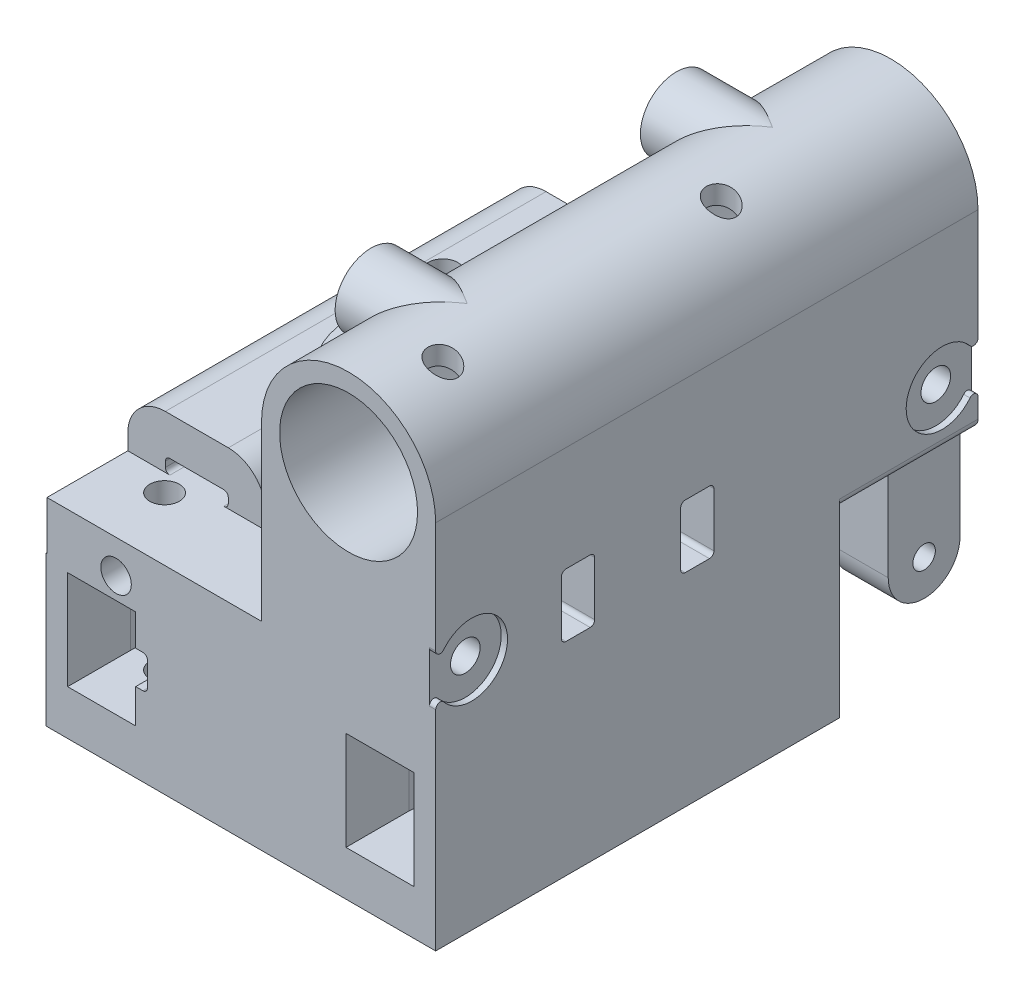
SolidWorks part; units mm, degrees
ref_plane "Front Plane" through (0, 0, 0) normal (0, 0, 1) x (1, 0, 0)
ref_plane "Top Plane" through (0, 0, 0) normal (0, 1, 0) x (1, 0, 0)
ref_plane "Right Plane" through (0, 0, 0) normal (1, 0, 0) x (0, 0, -1)
sketch "Sketch1" plane through (0, 0, 0) normal (0, 0, 1) x (1, 0, 0)
  line L57 (9.7, 0) -> (9.7, -41.3)
  line L61 (-29.4, -32) -> (-29.4, -29.3)
  line L62 (-29.4, -18.1) -> (-29.4, -18.7)
  line L63 (-28.9, -19.2) -> (-22.9, -19.2)
  line L64 (-22.4, -18.7) -> (-22.4, -18.1)
  line L65 (-22.9, -17.6) -> (-28.9, -17.6)
  line L66 (-28.9, -32.5) -> (-22.9, -32.5)
  line L67 (-22.4, -32) -> (-22.4, -29.3)
  line L68 (-28.9, -28.8) -> (-22.9, -28.8)
  line L76 (-9.7, -19.2) -> (-9.7, 0)
  line L77 (9.7, -41.3) -> (-33.7, -41.3)
  line L84 (-9.7, -19.2) -> (-18.21, -19.2)
  line L85 (-33.59, -17.49) -> (-33.59, -24.62)
  line L86 (-33.7, -24.62) -> (-33.7, -41.3)
  line L87 (-33.59, -24.62) -> (-33.7, -24.62)
  line L88 (-18.21, -19.2) -> (-18.21, -17.49)
  line L96 (-22.39, -13.31) -> (-29.41, -13.31)
  circle A0 centre (0, 0) radius 7.68
  arc A39 (9.7, 0) -> (-9.7, 0) centre (0, 0) ccw
  circle A59 centre (-25.9, -22.91) radius 1.7
  arc A60 (-28.9, -17.6) -> (-29.4, -18.1) centre (-28.9, -18.1) ccw
  arc A61 (-29.4, -18.7) -> (-28.9, -19.2) centre (-28.9, -18.7) ccw
  arc A62 (-22.9, -19.2) -> (-22.4, -18.7) centre (-22.9, -18.7) ccw
  arc A63 (-22.4, -18.1) -> (-22.9, -17.6) centre (-22.9, -18.1) ccw
  arc A64 (-29.4, -29.3) -> (-28.9, -28.8) centre (-28.9, -29.3) cw
  arc A65 (-22.4, -29.3) -> (-22.9, -28.8) centre (-22.9, -29.3) ccw
  arc A66 (-22.9, -32.5) -> (-22.4, -32) centre (-22.9, -32) ccw
  arc A67 (-29.4, -32) -> (-28.9, -32.5) centre (-28.9, -32) ccw
  arc A87 (-33.59, -17.49) -> (-29.41, -13.31) centre (-29.41, -17.49) cw
  arc A88 (-22.39, -13.31) -> (-18.21, -17.49) centre (-22.39, -17.49) cw
extrude "Boss-Extrude1" add sketch "Sketch1" along normal blind 60.4
sketch "Sketch8" plane through (0, -41.3, 0) normal (0, 1, 0) x (1, 0, 0)
  line L6 (-12, -48.01) -> (-7.68, -48.01)
  line L8 (-12, -27.79) -> (-7.68, -27.79)
  line L9 (-7.68, -48.01) -> (-7.68, -27.79)
  arc A1 (-12, -27.79) -> (-12, -48.01) centre (-12, -37.9) ccw
extrude "Boss-Extrude3" add sketch "Sketch8" along normal blind 34.02
sketch "Sketch2" plane through (0, 0, 0) normal (0, 0, -1) x (-1, 0, 0)
  line L0 (22.39, -15.34) -> (29.41, -15.34)
  line L1 (20.24, -17.49) -> (20.24, -24.62)
  line L2 (22.39, -26.77) -> (29.41, -26.77)
  line L3 (31.56, -17.49) -> (31.56, -24.62)
  arc A1 (22.39, -15.34) -> (20.24, -17.49) centre (22.39, -17.49) ccw
  arc A2 (31.56, -17.49) -> (29.41, -15.34) centre (29.41, -17.49) ccw
  arc A3 (29.41, -26.77) -> (31.56, -24.62) centre (29.41, -24.62) ccw
  arc A4 (20.24, -24.62) -> (22.39, -26.77) centre (22.39, -24.62) ccw
sketch "Sketch3" plane through (9.7, 0, 0) normal (1, 0, 0) x (0, 0, -1)
  line L11 (-46.39, -12.2) -> (-46.39, -18.2)
  line L12 (-43.19, -18.7) -> (-45.89, -18.7)
  line L13 (-42.69, -12.2) -> (-42.69, -18.2)
  line L14 (-43.19, -11.7) -> (-45.89, -11.7)
  line L15 (-33.11, -12.2) -> (-33.11, -18.2)
  line L16 (-29.91, -18.7) -> (-32.61, -18.7)
  line L17 (-29.41, -12.2) -> (-29.41, -18.2)
  line L18 (-29.91, -11.7) -> (-32.61, -11.7)
  circle A10 centre (-4, -15.2) radius 1.65
  circle A11 centre (-56.4, -15.2) radius 1.65
  arc A12 (-29.91, -11.7) -> (-29.41, -12.2) centre (-29.91, -12.2) cw
  arc A13 (-29.41, -18.2) -> (-29.91, -18.7) centre (-29.91, -18.2) cw
  arc A14 (-32.61, -18.7) -> (-33.11, -18.2) centre (-32.61, -18.2) cw
  arc A15 (-32.61, -11.7) -> (-33.11, -12.2) centre (-32.61, -12.2) ccw
  arc A16 (-43.19, -11.7) -> (-42.69, -12.2) centre (-43.19, -12.2) cw
  arc A17 (-42.69, -18.2) -> (-43.19, -18.7) centre (-43.19, -18.2) cw
  arc A18 (-45.89, -18.7) -> (-46.39, -18.2) centre (-45.89, -18.2) cw
  arc A19 (-45.89, -11.7) -> (-46.39, -12.2) centre (-45.89, -12.2) ccw
sketch "Sketch4" plane through (0, -41.3, 0) normal (0, -1, 0) x (1, 0, 0)
  circle A0 centre (-12, 37.9) radius 8.49
extrude "Cut-Extrude1" cut sketch "Sketch4" against normal blind 32
sketch "Sketch6" plane through (0, -41.3, 0) normal (0, -1, 0) x (1, 0, 0)
  circle A1 centre (3.5, 53.4) radius 1.65
  circle A2 centre (-27.5, 53.4) radius 1.65
  circle A3 centre (-27.5, 22.4) radius 1.65
  circle A4 centre (3.5, 22.4) radius 1.65
extrude "Cut-Extrude2" cut sketch "Sketch2" against normal blind 30.2
extrude "Cut-Extrude4" cut sketch "Sketch3" against normal up to next
sketch "Sketch9" plane through (9.7, 0, 0) normal (1, 0, 0) x (0, 0, -1)
  line L0 (-60.4, -12.3716) -> (-60.4, -18.0284)
  line L1 (0, -12.3716) -> (0, -18.0284)
  arc A0 (-60.4, -12.3716) -> (-59.5111, -12.6858) centre (-59.9, -12.3716) ccw
  arc A1 (-59.5111, -17.7142) -> (-59.5111, -12.6858) centre (-56.4, -15.2) ccw
  arc A2 (-59.5111, -17.7142) -> (-60.4, -18.0284) centre (-59.9, -18.0284) ccw
  arc A3 (-0.8889, -17.7142) -> (0, -18.0284) centre (-0.5, -18.0284) cw
  arc A4 (-0.8889, -17.7142) -> (-0.8889, -12.6858) centre (-4, -15.2) cw
  arc A5 (0, -12.3716) -> (-0.8889, -12.6858) centre (-0.5, -12.3716) cw
extrude "Cut-Extrude5" cut sketch "Sketch9" against normal blind 0.7
sketch "Sketch10" plane through (-9.7, 0, 0) normal (-1, 0, 0) x (0, 0, 1)
  circle A0 centre (4, -15.2) radius 3.6
  circle A1 centre (56.4, -15.2) radius 3.6
extrude "Cut-Extrude6" cut sketch "Sketch10" against normal blind 0.4
sketch "Sketch14" plane through (0, 0, 0) normal (0, 0, -1) x (-1, 0, 0)
  line L3 (-9.7, -20.2) -> (-9.7, -41.3)
  line L12 (-9.7, -41.3) -> (33.7, -41.3)
  line L16 (-8.7, -21.2) -> (8.7, -21.2)
  line L18 (9.7, -19.2) -> (18.21, -19.2)
  line L19 (9.7, -19.2) -> (9.7, -20.2)
  line L32 (22.39, -28.8) -> (29.41, -28.8)
  line L34 (18.21, -24.62) -> (18.21, -19.2)
  line L37 (33.59, -24.62) -> (33.7, -24.62)
  line L39 (33.7, -24.62) -> (33.7, -41.3)
  arc A10 (-9.7, -20.2) -> (-8.7, -21.2) centre (-8.7, -20.2) ccw
  arc A11 (8.7, -21.2) -> (9.7, -20.2) centre (8.7, -20.2) ccw
  arc A23 (29.41, -28.8) -> (33.59, -24.62) centre (29.41, -24.62) ccw
  arc A25 (18.21, -24.62) -> (22.39, -28.8) centre (22.39, -24.62) ccw
sketch "Sketch15" plane through (0, 0, 0) normal (0, 0, -1) x (-1, 0, 0)
  line L1 (22.39, -13.2) -> (29.41, -13.2)
  line L3 (22.39, -28.91) -> (29.41, -28.91)
  line L12 (18.1, -17.49) -> (18.1, -24.62)
  line L14 (33.7, -17.49) -> (33.7, -24.62)
  arc A4 (22.39, -13.2) -> (18.1, -17.49) centre (22.39, -17.49) ccw
  arc A5 (33.7, -17.49) -> (29.41, -13.2) centre (29.41, -17.49) ccw
  arc A9 (29.41, -28.91) -> (33.7, -24.62) centre (29.41, -24.62) ccw
  arc A10 (18.1, -24.62) -> (22.39, -28.91) centre (22.39, -24.62) ccw
extrude "Cut-Extrude8" cut sketch "Sketch14" against normal blind 15.4
extrude "Cut-Extrude9" cut sketch "Sketch15" against normal blind 9
extrude "Cut-Extrude10" cut sketch "Sketch6" against normal through all
sketch "Sketch16" plane through (0, -41.3, 0) normal (0, -1, 0) x (1, 0, 0)
  circle A0 centre (-12, 37.9) radius 11.5
extrude "Cut-Extrude11" cut sketch "Sketch16" against normal blind 2.5
sketch "Sketch17" plane through (0, 0, 60.4) normal (0, 0, 1) x (1, 0, 0)
  line L9 (-29.41, -13.31) -> (-22.39, -13.31)
  line L12 (-33.59, -17.49) -> (-33.59, -19.2)
  line L13 (-33.59, -19.2) -> (-18.21, -19.2)
  line L14 (-18.21, -17.49) -> (-18.21, -19.2)
  arc A8 (-18.21, -17.49) -> (-22.39, -13.31) centre (-22.39, -17.49) ccw
  arc A9 (-29.41, -13.31) -> (-33.59, -17.49) centre (-29.41, -17.49) ccw
extrude "Cut-Extrude12" cut sketch "Sketch17" against normal blind 9
sketch "Sketch12" plane through (0, -41.3, 0) normal (0, -1, 0) x (1, 0, 0)
  line L38 (-31.29, 53.4) -> (-31.29, 60.4)
  line L43 (-31.29, 60.4) -> (-23.71, 60.4)
  line L44 (-23.71, 53.4) -> (-23.71, 60.4)
  line L47 (-0.29, 53.4) -> (-0.29, 60.4)
  line L48 (-0.29, 60.4) -> (7.29, 60.4)
  line L49 (7.29, 53.4) -> (7.29, 60.4)
  line L51 (-0.29, 22.4) -> (-0.29, 15.4)
  line L52 (-0.29, 15.4) -> (7.29, 15.4)
  line L53 (7.29, 22.4) -> (7.29, 15.4)
  circle A5 centre (-27.5, 22.4) radius 3.79
  arc A12 (-31.29, 53.4) -> (-23.71, 53.4) centre (-27.5, 53.4) ccw
  arc A13 (-0.29, 53.4) -> (7.29, 53.4) centre (3.5, 53.4) ccw
  arc A14 (7.29, 22.4) -> (-0.29, 22.4) centre (3.5, 22.4) ccw
extrude "Cut-Extrude13" cut sketch "Sketch12" against normal blind 11 from offset 5 offset against normal yes
sketch "Sketch20" plane through (-9.7, 0, 0) normal (-1, 0, 0) x (0, 0, 1)
  circle A0 centre (13.2, 5.7) radius 4
  circle A1 centre (47.2, 5.7) radius 4
extrude "Boss-Extrude4" add sketch "Sketch20" against normal up to surface and the other way blind 1 up to face at (3.0891, 9.195, 23.998)
sketch "Sketch19" plane through (-10.7, 0, 0) normal (-1, 0, 0) x (0, 0, 1)
  circle A0 centre (13.2, 5.7) radius 1.65
  circle A1 centre (47.2, 5.7) radius 1.65
extrude "Cut-Extrude14" cut sketch "Sketch19" against normal up to next
sketch "Sketch21" plane through (9.7, 0, 0) normal (1, 0, 0) x (0, 0, -1)
  line L7 (-8, -32.5) -> (-8, -21.2)
  line L8 (-8, -21.2) -> (0, -21.2)
  line L9 (0, -32.5) -> (0, -21.2)
  circle A0 centre (-4, -32.5) radius 1.25
  arc A1 (-8, -32.5) -> (0, -32.5) centre (-4, -32.5) ccw
extrude "Boss-Extrude5" add sketch "Sketch21" against normal blind 6 from offset 2 offset against normal yes
sketch "Sketch22" plane through (0, 0, 30.2) normal (0, 0, -1) x (-1, 0, 0)
  line L0 (22.9, -16.9) -> (28.9, -16.9)
  line L1 (22.4, -17.4) -> (22.4, -18.7)
  line L2 (22.9, -19.2) -> (28.9, -19.2)
  line L3 (29.4, -17.4) -> (29.4, -18.7)
  arc A0 (28.9, -19.2) -> (29.4, -18.7) centre (28.9, -18.7) ccw
  arc A1 (29.4, -17.4) -> (28.9, -16.9) centre (28.9, -17.4) ccw
  arc A2 (22.9, -16.9) -> (22.4, -17.4) centre (22.9, -17.4) ccw
  arc A3 (22.9, -19.2) -> (22.4, -18.7) centre (22.9, -18.7) cw
extrude "Cut-Extrude15" cut sketch "Sketch22" against normal blind 8
